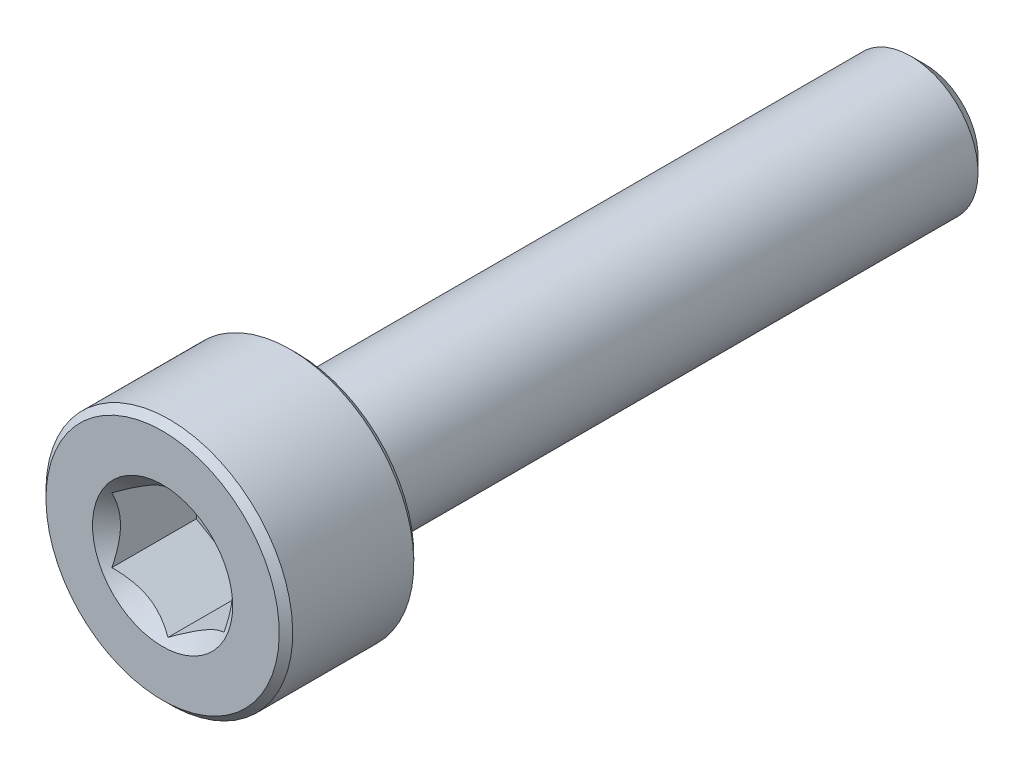
SolidWorks part; units mm, degrees
ref_plane "Front Plane" through (0, 0, 0) normal (0, 0, 1) x (1, 0, 0)
ref_plane "Top Plane" through (0, 0, 0) normal (0, 1, 0) x (1, 0, 0)
ref_plane "Right Plane" through (0, 0, 0) normal (1, 0, 0) x (0, 0, -1)
sketch "Sketch1" plane through (0, 0, 0) normal (1, 0, 0) x (0, 0, -1)
  line L0 (-8.5, 0) -> (8.5, 0) construction
  line L1 (8.5, 0) -> (8.5, 1.1752) construction
  line L2 (8.5, 1.1752) -> (8.1752, 1.5) construction
  line L3 (8.1752, 1.5) -> (8.125, 1.5) construction
  line L4 (8.125, 1.5) -> (-5.5, 1.5) construction
  line L5 (-5.5, 1.5) -> (-5.5, 2.75) construction
  line L6 (-5.5, 2.75) -> (-8.5, 2.75) construction
  line L7 (-8.5, 2.75) -> (-8.5, 0) construction
  line L8 (8.5, 1.1752) -> (8.5, 1.5) construction
  line L9 (8.4688, 1.5541) -> (8.7188, 1.1211) construction
  line L10 (8.7188, 1.1211) -> (8.9688, 1.5541) construction
  line L11 (8.9688, 1.5541) -> (8.4688, 1.5541) construction
  line L12 (8.7188, 1.5541) -> (8.7188, 1.5) construction
  line L13 (8.7188, 1.1211) -> (8.7188, 1.1752) construction
  line L14 (8.6875, 1.1752) -> (8.75, 1.1752) construction
  line L15 (8.5, 1.5) -> (8.9375, 1.5) construction
  line L16 (8.4844, 1.5271) -> (8.9531, 1.5271) construction
  line L17 (8.5, 0) -> (8.5, -1.5) construction
  line L18 (-5.65, 2.75) -> (-5.5, 2.6) construction
  line L19 (-8.35, 2.75) -> (-8.5, 2.6) construction
  line L20 (-5.5, 1.5) -> (-5.5, 0) construction
  line L21 (-5.5, 0.75) -> (-0.8333, 0.75) construction
  line L22 (-0.8333, 0.75) -> (3.8333, 0.75) construction
  line L23 (3.8333, 0.75) -> (8.5, 0.75) construction
  line L24 (-0.8333, 0.75) -> (-0.8333, 1.5) construction
  line L25 (-0.8333, 1.5) -> (-0.8333, 2.75) construction
  line L26 (3.8333, 0.75) -> (3.8333, 2.75) construction
  point P0 (-8.5, 1.25)
  point P3 (7.25, 1.5)
  point P4 (0, 0)
  point P18 (3.8333, 1.5)
  point P22 (8.7188, 1.1752)
  point P24 (8.125, 1.5)
  point P25 (8.7188, 1.5)
  point P28 (8.7188, 1.5271)
  point P29 (7.25, -1.5)
  point P30 (-0.8333, 1.5)
  point P31 (-7, 2.75)
  point P37 (-6.025, 2.75)
  point P38 (-8.275, 2.75)
  point P45 (-0.8333, 0.75)
  point P46 (3.8333, 0.75)
  dimension "D2" = 0.0625
  dimension "D7" = 0.15
  dimension "D8" = 0.15
  dimension "D9" = 0.15
  dimension "D10" = 0.075
  dimension "D11" = 0.375
  dimension "Drive Size" = 2.5
  dimension "Head Diameter" = 5.5
  dimension "Head Height" = 3
  dimension "Thread Pitch" = 0.5
  dimension "Thread Size" = 3
  dimension "Length" = 14
  dimension "D12" = 0.375
  dimension "D4" = 1.25
  dimension "D3" = 45
sketch "Sketch2" plane through (0, 0, 0) normal (1, 0, 0) x (0, 0, -1)
  line L0 (-8.5, 0) -> (-8.5, 2.6)
  line L1 (-8.35, 2.75) -> (-5.65, 2.75)
  line L2 (-5.5, 2.6) -> (-5.5, 1.65)
  line L4 (8.1752, 1.5) -> (8.5, 1.1752)
  line L5 (8.5, 1.1752) -> (8.5, 0)
  line L6 (-5.5, 2.75) -> (-8.5, 2.75) construction
  line L7 (8.5, 0) -> (-8.5, 0)
  line L8 (-8.35, 2.75) -> (-8.5, 2.6) construction
  line L10 (-8.35, 2.75) -> (-8.5, 2.6)
  line L14 (-5.65, 2.75) -> (-5.5, 2.6) construction
  line L16 (-5.65, 2.75) -> (-5.5, 2.6)
  line L17 (-5.5, 1.5) -> (-5.5, 2.75) construction
  line L19 (-5.35, 1.5) -> (8.1752, 1.5)
  line L20 (8.125, 1.5) -> (-5.5, 1.5) construction
  arc A1 (-5.5, 1.65) -> (-5.35, 1.5) centre (-5.35, 1.65) ccw
  dimension "D3" = 0.15
revolve "Revolve1" add sketch "Sketch2" angle 360 about L7
sketch "Sketch3" plane through (0, 0, 8.5) normal (0, 0, 1) x (1, 0, 0)
  line L1 (1.25, -0.7217) -> (1.25, 0.7217)
  line L2 (1.25, 0.7217) -> (0, 1.4434)
  line L3 (0, 1.4434) -> (-1.25, 0.7217)
  line L4 (-1.25, 0.7217) -> (-1.25, -0.7217)
  line L5 (-1.25, -0.7217) -> (0, -1.4434)
  line L6 (0, -1.4434) -> (1.25, -0.7217)
  circle A0 centre (0, 0) radius 1.25 construction
  circle A1 centre (0, 0) radius 2.75 construction
  circle A2 centre (0, 0) radius 2.75 construction
  circle A3 centre (0, 0) radius 1.4434 construction
  point P13 (0, 0)
extrude "Cut-Extrude1" cut sketch "Sketch3" against normal offset from surface (2 mm away) 1 up to face at (0, 2.6, 5.5)
sketch "Sketch4" plane through (0, 0, 8.5) normal (0, 0, 1) x (1, 0, 0)
  circle A0 centre (0, 0) radius 1.5625
  dimension "D1" = 3.125
extrude "Cut-Extrude2" cut sketch "Sketch4" against normal up to vertex (1.5 mm away) draft 45 up to point (0, 2.75, 7)
sketch "Sketch11" plane through (0, 0, 0) normal (1, 0, 0) x (0, 0, -1)
  line L0 (-8.5, 0) -> (8.5, 0) construction
  line L1 (-8.5, 0) -> (8.5, 0) construction
  line L2 (-2.875, 0) -> (-2.875, 1.5) construction
  line L3 (8.125, 1.5) -> (-5.5, 1.5) construction
  line L4 (5.875, 0) -> (5.875, 1.5) construction
  line L6 (8.5, 1.1752) -> (8.5, 1.5) construction
  point P2 (-2.875, 0)
  point P3 (5.875, 0)
  dimension "D1" = 2.625
  dimension "D2" = 2.625
sketch "Sketch6" [suppressed] plane through (0, 0, -8.5) normal (0, 0, -1) x (-1, 0, 0)
  circle A0 centre (0, 0) radius 1.5
curve "Helix/Spiral1" [suppressed] pitch 0.5 height 14.5 turns 29
sketch "Sketch10" [suppressed] plane through (0, 0, 0) normal (1, 0, 0) x (0, 0, -1)
  line L0 (-5.35, -2.75) -> (-5.35, 2.75)
  line L5 (-8.5, 0) -> (8.5, 0) construction
  line L6 (-5.35, 1.5) -> (-5.35, -1.5) construction
  point P3 (-5.35, 0)
split "Split1" [suppressed] bodies to split 106
sketch "Sketch7" [suppressed] plane through (0, 0, 0) normal (1, 0, 0) x (0, 0, -1)
  line L0 (8.4844, 1.5271) -> (8.9531, 1.5271)
  line L1 (8.9531, 1.5271) -> (8.75, 1.1752)
  line L2 (8.75, 1.1752) -> (8.6875, 1.1752)
  line L3 (8.6875, 1.1752) -> (8.4844, 1.5271)
sweep "Cut-Sweep1" [suppressed] cut profiles "Sketch7" path "Helix/Spiral1"
sketch "Sketch8" [suppressed] plane through (0, 0, 0) normal (1, 0, 0) x (0, 0, -1)
  line L0 (-5.5, 0) -> (-5.5, 1.5)
  line L1 (-5.35, -1.5) -> (-5.35, 1.5) construction
  line L2 (-5.5, 1.5) -> (-5.35, 1.5)
  line L4 (-5.35, 1.5) -> (-4.484, 0)
  line L5 (-4.484, 0) -> (-5.5, 0)
  line L6 (8.125, 1.5) -> (-5.5, 1.5) construction
  line L7 (-8.5, 0) -> (8.5, 0) construction
  dimension "D1" = 60
revolve "Revolve2" [suppressed] add sketch "Sketch8" angle 360 about L5
ref_plane "Plane1" [suppressed] through (0, 0, 8.5) normal (0, 0, 1) x (1, 0, 0)
sketch "Sketch12" [suppressed] plane through (0, 0, 8.5) normal (0, 0, 1) x (1, 0, 0)
  line L0 (0, 0) -> (0.096, 2.7483) construction
  line L1 (0, 0) -> (-0.096, 2.7483) construction
  line L2 (0, 2.6812) -> (0, 2.8187) construction
  line L3 (-0.1664, 2.8187) -> (0.1664, 2.8187)
  line L4 (-0.1664, 2.8187) -> (-0.0493, 2.7017)
  line L5 (0.0493, 2.7017) -> (0.1664, 2.8187)
  circle A0 centre (0, 0) radius 2.75 construction
  arc A1 (-0.0493, 2.7017) -> (0.0493, 2.7017) centre (0, 2.751) ccw
  point P9 (0, 2.8187)
  point P13 (0, 2.75)
  dimension "D1" = 4
  dimension "D2" = 0.0688
extrude "Cut-Extrude3" [suppressed] cut sketch "Sketch12" against normal blind 2.4
pattern_circular "CirPattern1" [suppressed] count 72 over 360 about axis through (0, 0, 8.5) along (0, 0, -1) of bodies 118
equation "\"D2@Sketch1\" = \"Thread Pitch@Sketch1\" / 8"
equation "\"D4@Helix/Spiral1\" = \"Thread Pitch@Sketch1\""
equation "\"D7@Sketch1\" = \"Head Height@Sketch1\" * .05"
equation "\"D8@Sketch1\"=\"D7@Sketch1\""
equation "\"D9@Sketch1\"=\"D7@Sketch1\""
equation "\"D10@Sketch1\"=\"D7@Sketch1\"/2"
equation "\"D11@Sketch1\"=\"D10@Sketch1\"*5"
equation "\"D4@Sketch1\"=\"Thread Pitch@Sketch1\"*2.5"
equation "\"D12@Sketch1\"=\"Thread Pitch@Sketch1\"*.75"
equation "\"D3@Helix/Spiral1\"=\"Length@Sketch1\"+\"Thread Pitch@Sketch1\""
equation "\"D3@Sketch2\" = \"Thread Size@Sketch1\" * 0.05"
equation "\"D1@Sketch11\"=\"Length@Sketch1\"*0.1875"
equation "\"D2@Sketch11\"=\"D1@Sketch11\""
equation "\"D2@Sketch12\"=\"Head Diameter@Sketch1\"*.0125"
equation "\"D1@Cut-Extrude3\"=\"Head Height@Sketch1\"*.8"
equation "\"D1@CirPattern1\"=\"D3@CirPattern1\"/(1.25*\"D1@Sketch12\")"
equation "\"D1@Sketch4\"=\"Drive Size@Sketch1\"*1.25"
